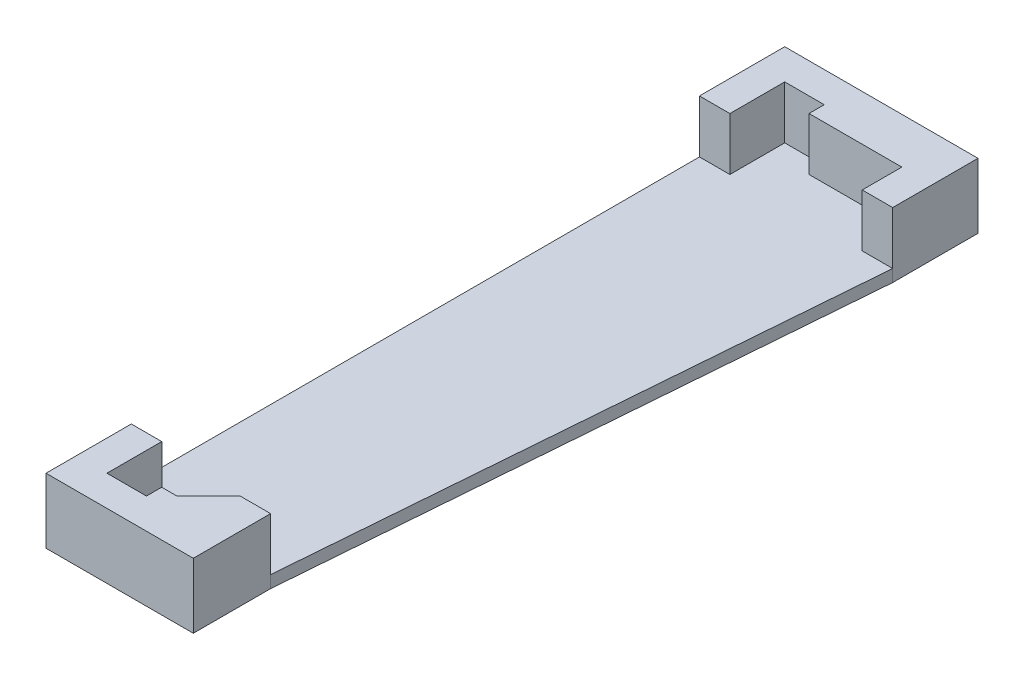
SolidWorks part; units mm, degrees
ref_plane "Front Plane" through (0, 0, 0) normal (0, 0, 1) x (1, 0, 0)
ref_plane "Top Plane" through (0, 0, 0) normal (0, 1, 0) x (1, 0, 0)
ref_plane "Right Plane" through (0, 0, 0) normal (1, 0, 0) x (0, 0, -1)
sketch "Sketch1" plane through (0, 0, 0) normal (0, 1, 0) x (1, 0, 0)
  line L1 (0, 0) -> (40.2874, 0)
  line L2 (0, 0) -> (0, 153.9875)
  line L3 (0, 153.9875) -> (40.2874, 153.9875)
  line L4 (40.2874, 0) -> (40.2874, 153.9875)
  dimension "D1" = 40.2874
  dimension "D2" = 153.9875
extrude "Boss-Extrude1" add sketch "Sketch1" along normal blind 2.54
sketch "Sketch3" plane through (0, 2.54, 0) normal (0, 1, 0) x (1, 0, 0)
  line L0 (6.65, 147.6375) -> (6.35, 147.6375)
  line L1 (6.65, 147.6375) -> (14.5875, 147.6375)
  line L2 (14.5875, 147.6375) -> (14.5875, 144.4625)
  line L3 (14.5875, 144.4625) -> (33.6375, 144.4625)
  line L4 (6.35, 147.6375) -> (6.35, 136.2075)
  line L7 (33.6375, 144.4625) -> (33.9375, 144.4625)
  line L8 (33.9375, 144.4625) -> (33.9375, 136.2075)
  line L9 (33.9375, 136.2075) -> (40.2875, 136.2075)
  line L10 (40.2875, 136.2075) -> (40.2875, 153.9875)
  line L11 (40.2875, 153.9875) -> (0, 153.9875)
  line L12 (6.35, 136.2075) -> (0, 136.2075)
  line L13 (0, 153.9875) -> (0, 136.2075)
  line L14 (40.2874, 153.9875) -> (0, 153.9875) construction
  line L15 (0, 153.9875) -> (0, 0) construction
  line L16 (14.5875, 9.525) -> (17.7625, 9.525)
  line L17 (10.6187, 147.6375) -> (10.6187, 76.9938) construction
  line L18 (10.6187, 76.9938) -> (61.4187, 76.9938) construction
  line L19 (30.7032, 0) -> (0, 0)
  line L20 (30.7032, 16.1157) -> (30.7032, 0)
  line L25 (14.5875, 6.35) -> (14.5875, 9.525)
  line L26 (6.65, 6.35) -> (14.5875, 6.35)
  line L27 (6.65, 6.35) -> (6.35, 6.35)
  line L28 (6.35, 6.35) -> (6.35, 17.78)
  line L29 (6.35, 17.78) -> (0, 17.78)
  line L30 (0, 0) -> (0, 17.78)
  line L31 (17.7625, 9.525) -> (24.3532, 16.1157)
  line L32 (24.3532, 16.1157) -> (30.7032, 16.1157)
  point P19 (10.6187, 147.6375)
  line M5 (40.2874, 153.9875) -> (0, 153.9875)
  dimension "D1" = 19.05
  dimension "D2" = 7.9375
  dimension "D3" = 3.175
  dimension "D4" = 11.43
  dimension "D5" = 0.3
  dimension "D6" = 0.3
  dimension "D7" = 0
  dimension "D8" = 0
  dimension "D9" = 6.35
  dimension "D10" = 6.35
  dimension "D11" = 6.35
  dimension "D12" = 0
  dimension "D13" = 70.6437
  dimension "D14" = 50.8
  dimension "D15" = 3.175
  dimension "D16" = 135
  dimension "D17" = 6.35
  dimension "D18" = 90
  dimension "D19" = 18.08
  dimension "D20" = 90
extrude "Boss-Extrude2" add sketch "Sketch3" along normal blind 11.0067 contours L13 L12 L4 L0 L1 L2 L3 L7 L8 L9 L10 M5 | L30 L19 L20 L25 L26 L27 L28 L29 region at (20.691, 2.54, -147.3891) region at (15.7357, 2.54, -7.0418)
sketch "Sketch4" plane through (0, 2.54, 0) normal (0, 1, 0) x (1, 0, 0)
  line L0 (30.7032, 0) -> (40.2874, 0)
  line L1 (40.2874, 0) -> (40.2874, 136.2075)
  line L3 (40.2874, 136.2075) -> (30.7032, 16.1157)
  line L4 (30.7032, 16.1157) -> (30.7032, 0)
extrude "Cut-Extrude1" cut sketch "Sketch4" against normal through all
